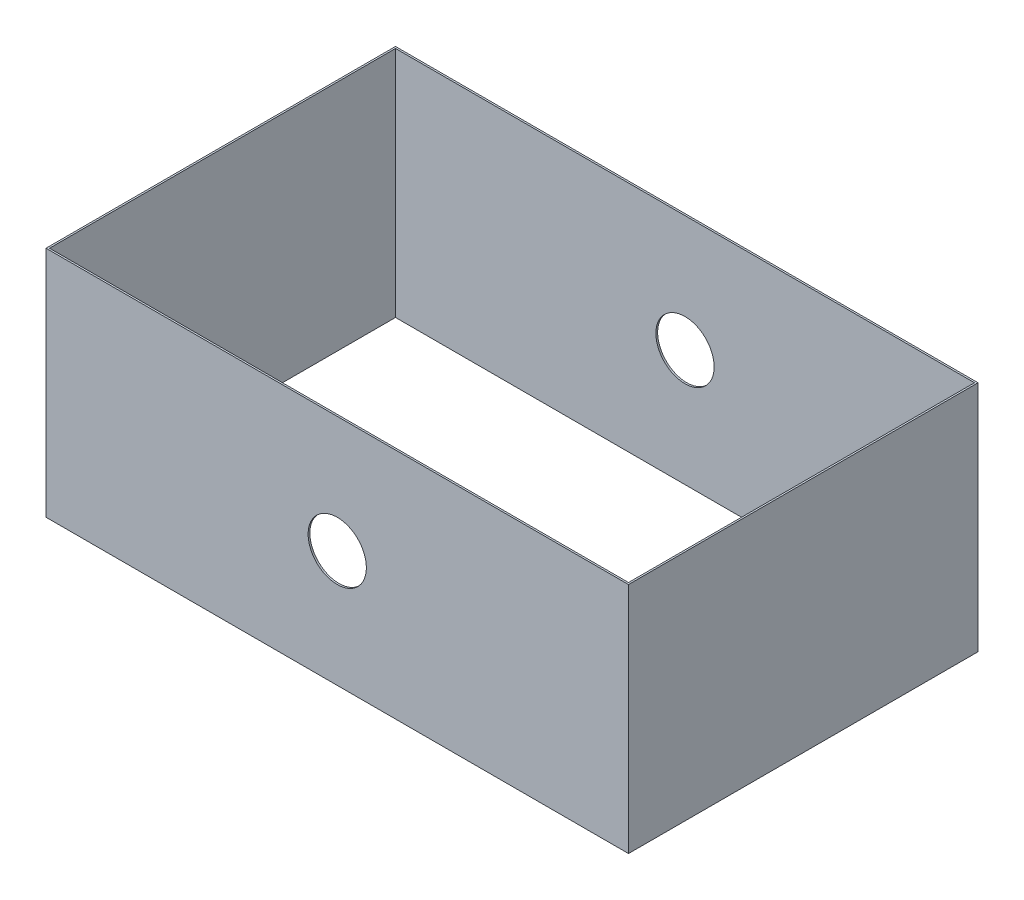
SolidWorks part; units mm, degrees
ref_plane "Front Plane" through (0, 0, 0) normal (0, 0, 1) x (1, 0, 0)
ref_plane "Top Plane" through (0, 0, 0) normal (0, 1, 0) x (1, 0, 0)
ref_plane "Right Plane" through (0, 0, 0) normal (1, 0, 0) x (0, 0, -1)
sketch "Sketch1" plane through (0, 0, 0) normal (0, 0, 1) x (1, 0, 0)
  line L1 (250, -100) -> (-250, -100)
  line L2 (250, -100) -> (250, 100)
  line L3 (250, 100) -> (-250, 100)
  line L4 (-250, -100) -> (-250, 100)
  line L5 (250, -100) -> (-250, 100) construction
  line L6 (250, 100) -> (-250, -100) construction
  circle A0 centre (0, 0) radius 25
  point P0 (0, 0)
  dimension "D3" = 50
  dimension "D1" = 200
  dimension "D2" = 500
extrude "Boss-Extrude1" add sketch "Sketch1" along normal blind 300
sketch "Sketch2" plane through (0, 100, 0) normal (0, 1, 0) x (1, 0, 0)
  line L0 (-250, -150) -> (250, -150) construction
  line L1 (-250, -300) -> (-250, 0) construction
  line L2 (250, -300) -> (250, 0) construction
  line L3 (250, 0) -> (-250, 0) construction
  line L4 (248.5, -298.5) -> (-248.5, -298.5)
  line L5 (248.5, -298.5) -> (248.5, -1.5)
  line L6 (248.5, -1.5) -> (-248.5, -1.5)
  line L7 (-248.5, -298.5) -> (-248.5, -1.5)
  line L8 (248.5, -298.5) -> (-248.5, -1.5) construction
  line L9 (248.5, -1.5) -> (-248.5, -298.5) construction
  point P6 (0, -150)
  dimension "D1" = 1.5
  dimension "D2" = 1.5
extrude "Cut-Extrude1" cut sketch "Sketch2" against normal through all
equation "\"rover_width\"= 800.0mm"
equation "\"rover_length\"= 1000.0mm"
equation "\"frame_width\"= 300.0mm"
equation "\"frame_height\"= 200.0mm"
equation "\"ground_clearance\"= 310.0mm"
equation "\"swingarm_thickness\"= 5.0mm"
equation "\"steering_asm_height\"= 90.92mm"
equation "\"rear_steering_mount_neck_height\"= 30.0mm"
equation "\"front_steering_mount_base_length\"= 81.18035315337238mm"
equation "\"corner_wheel_asm_height\"= 250.0mm"
equation "\"middle_wheel_shaft_diameter\"= 41.97mm"
equation "\"middle_wheel_shaft_length\"= 110.0mm"
equation "\"middle_wheel_shaft_overhang\"= 10.0mm"
equation "\"middle_wheel_clearance\"= 4.0mm"
equation "\"wheel_diameter\"= 200.0mm"
equation "\"wheel_thickness\"= 80.0mm"
equation "\"linkage_thickness\"= 18.0mm"
equation "\"linkage_width\"= 30.0mm"
equation "\"linkage_wall_thickness\"= 3.0mm"
equation "\"linkage_mount_base_length\"= 10.0mm"
equation "\"linkage_mount_bolt_diameter\"= 10.0mm"
equation "\"upper_shaft_diameter\"= 50.0mm"
equation "\"upper_shaft_frame_clearance\"= 4.0mm"
equation "\"upper_shaft_overhang\"= 4.0mm"
equation "\"lower_shaft_diameter\"= 35.0mm"
equation "\"lower_shaft_overhang\"= 4.5mm"
equation "\"pivot_housing_min_wall_thickness\"= 3.0mm"
equation "\"pivot_housing_bolt_diameter\"= 5.0mm"
equation "\"upper_pivot_housing_num_bolts\"= 12.0"
equation "\"lower_pivot_housing_num_bolts\"= 6.0"
equation "\"upper_bearing_diameter\"= 65.0mm"
equation "\"upper_bearing_outer_race_inner_diameter\"= 61.0mm"
equation "\"upper_bearing_thickness\"= 7.0mm"
equation "\"lower_bearing_diameter\"= 47.0mm"
equation "\"lower_bearing_outer_race_inner_diameter\"= 44.0mm"
equation "\"lower_bearing_thickness\"= 7.0mm"
equation "\"upper_ret_ring_inner_diameter\"= 45.8mm"
equation "\"upper_ret_ring_thickness\"= 2.0mm"
equation "\"lower_ret_ring_inner_diameter\"= 32.2mm"
equation "\"lower_ret_ring_thickness\"= 1.5mm"
equation "\"D1@Sketch1\"=\"frame_height\""
equation "\"D2@Sketch1\"=\"frame_height\"*2.5"
equation "\"D3@Sketch1\"=\"upper_shaft_diameter\""
equation "\"D1@Boss-Extrude1\"=\"frame_width\""
equation "\"frame_wall_thickness\"= 1.5mm"
equation "\"front_steering_mount_neck_height\"= 30.0mm"
equation "\"upper_shaft_min_wall_thickness\"= 3.0mm"
